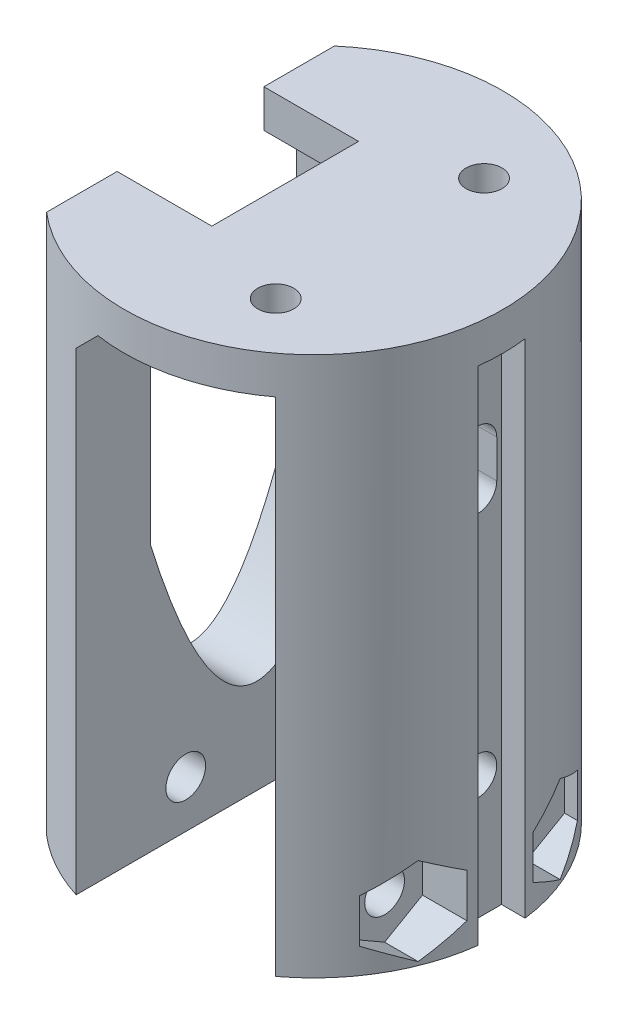
SolidWorks part; units mm, degrees
ref_plane "Front Plane" through (0, 0, 0) normal (0, 0, 1) x (1, 0, 0)
ref_plane "Top Plane" through (0, 0, 0) normal (0, 1, 0) x (1, 0, 0)
ref_plane "Right Plane" through (0, 0, 0) normal (1, 0, 0) x (0, 0, -1)
sketch "Sketch2" plane through (0, 0, 0) normal (0, 1, 0) x (1, 0, 0)
  line L0 (-3.81, 25.1126) -> (-3.81, -25.1126) construction
  line L1 (-16.51, -19.3023) -> (-16.51, -9.8425)
  line L2 (-20.6326, -9.8425) -> (16.7847, -9.8425) construction
  line L3 (-16.51, -9.8425) -> (-3.81, -9.8425)
  line L4 (-3.81, -9.8425) -> (-3.81, 9.8425)
  line L5 (16.7847, 9.8425) -> (-20.6326, 9.8425) construction
  line L6 (-3.81, 9.8425) -> (-16.51, 9.8425)
  line L7 (-16.51, 9.8425) -> (-16.51, 19.3023)
  line L8 (-16.51, -19.3023) -> (-16.51, 19.3023) construction
  circle A2 centre (0, 0) radius 25.4 construction
  arc A3 (-16.51, -19.3023) -> (-16.51, 19.3023) centre (0, 0) ccw
  dimension "D1" = 3.81
  dimension "D2" = 16.51
  dimension "D3" = 25.4
extrude "plate" add sketch "Sketch2" along normal blind 5.08
sketch "Sketch15" plane through (0, 0, 0) normal (0, -1, 0) x (1, 0, 0)
  circle A1 centre (8.89, 13.97) radius 2.413
  circle A2 centre (8.89, 13.97) radius 2.413 construction
  circle A3 centre (8.89, -13.97) radius 2.413
  circle A4 centre (8.89, -13.97) radius 2.413 construction
extrude "boltholes" cut sketch "Sketch15" against normal up to next
sketch "Sketch16" plane through (0, 0, 0) normal (0, -1, 0) x (1, 0, 0)
  line L5 (25.2008, 3.175) -> (25.2008, -3.175) construction
  line L6 (15.24, 20.32) -> (15.24, -20.32)
  line L12 (0, 0) -> (25.2008, 0) construction
  line L13 (25.2008, 3.175) -> (22.0258, 3.175)
  line L14 (22.0258, 3.175) -> (22.0258, -3.175)
  line L15 (22.0258, -3.175) -> (25.2008, -3.175)
  arc A0 (-16.51, -19.3023) -> (-16.51, 19.3023) centre (0, 0) ccw construction
  arc A2 (15.24, 20.32) -> (25.2008, 3.175) centre (0, 0) cw
  arc A3 (15.24, -20.32) -> (25.2008, -3.175) centre (0, 0) ccw
  dimension "D1" = 6.35
  dimension "D4" = 15.24
  dimension "D2" = 3.175
extrude "upright" add sketch "Sketch16" along normal blind 67.31
sketch "Sketch19" plane through (0, 0, 0) normal (0, -1, 0) x (1, 0, 0)
  line L0 (-16.51, 14.2223) -> (-7.62, 14.2223)
  line L1 (-16.51, 9.8425) -> (-16.51, 19.3023) construction
  line L2 (-7.62, 14.2223) -> (-7.62, 24.2301)
  line L3 (-16.51, 19.3023) -> (-16.51, 14.2223)
  line L4 (-3.81, 0) -> (15.24, 0) construction
  line L5 (-3.81, -9.8425) -> (-3.81, 9.8425) construction
  line L6 (15.24, 20.32) -> (15.24, -20.32) construction
  line L7 (-7.62, -14.2223) -> (-7.62, -24.2301)
  line L8 (-16.51, -14.2223) -> (-7.62, -14.2223)
  line L9 (-16.51, -19.3023) -> (-16.51, -14.2223)
  line L10 (15.24, 20.32) -> (15.24, -20.32) construction
  arc A0 (15.24, 20.32) -> (-16.51, 19.3023) centre (0, 0) ccw construction
  arc A1 (-16.51, 19.3023) -> (-7.62, 24.2301) centre (0, 0) cw
  arc A2 (-16.51, -19.3023) -> (-7.62, -24.2301) centre (0, 0) ccw
  dimension "D1" = 8.89
  dimension "D2" = 5.08
  dimension "D3" = 22.86
  dimension "D4" = 7.62
extrude "second_side_legs" add sketch "Sketch19" along normal blind 31.75
sketch "Sketch20" plane through (0, -31.75, 0) normal (0, -1, 0) x (1, 0, 0)
  line L0 (-16.51, 19.3023) -> (-16.51, -19.3023)
  line L1 (-7.62, 24.2301) -> (-7.62, -24.2301)
  arc A0 (-16.51, 19.3023) -> (-7.62, 24.2301) centre (0, 0) cw
  arc A1 (-16.51, -19.3023) -> (-7.62, -24.2301) centre (0, 0) ccw
extrude "second_side_face" add sketch "Sketch20" along normal up to surface (35.56 mm away) up to face at (21.4029, -67.31, 0)
sketch "Sketch21" plane through (-16.51, 0, 0) normal (-1, 0, 0) x (0, 0, 1)
  line L0 (14.2223, -31.75) -> (-14.2223, -31.75) construction
  line L1 (-14.2223, -31.75) -> (-14.2223, 0) construction
  line L2 (0, -31.75) -> (0, -52.3979) construction
  line L3 (-14.2223, -31.75) -> (14.2223, -31.75)
  parabola Q0 (-14.2223, -31.75) -> (14.2223, -31.75) focus (0, -52.3979) apex (0, -54.61)
  dimension "D1" = 22.86
extrude "archway" cut sketch "Sketch21" against normal up to next
sketch "Sketch17" plane through (15.24, 0, 0) normal (-1, 0, 0) x (0, 0, 1)
  line L0 (0, 0) -> (0, -67.31) construction
  line L1 (-9.8425, 0) -> (9.8425, 0) construction
  line L2 (-3.175, -67.31) -> (3.175, -67.31) construction
  line L3 (0, -12.7) -> (0, -17.78) construction
  line L4 (2.54, -12.7) -> (2.54, -17.78)
  line L5 (-2.54, -12.7) -> (-2.54, -17.78)
  line L6 (-9.525, -60.96) -> (9.525, -60.96) construction
  arc A1 (2.54, -12.7) -> (-2.54, -12.7) centre (0, -12.7) ccw
  arc A2 (-2.54, -17.78) -> (2.54, -17.78) centre (0, -17.78) ccw
  circle A3 centre (0, -50.8) radius 2.54
  circle A6 centre (-9.525, -60.96) radius 2.667
  circle A7 centre (9.525, -60.96) radius 2.667
  point P8 (0, -15.24)
  point P17 (0, -60.96)
  dimension "D1" = 5.08
  dimension "D3" = 12.7
  dimension "D4" = 5.08
  dimension "D6" = 10.16
  dimension "D7" = 19.05
  dimension "D8" = 5.334
  dimension "D9" = 5.334
  dimension "D2" = 5.08
  dimension "D5" = 38.1
extrude "upright_holes" cut sketch "Sketch17" along normal through all both and the other way through all
sketch "Sketch22" plane through (15.24, 0, 0) normal (-1, 0, 0) x (0, 0, 1)
  line L1 (-9.525, -55.0941) -> (-14.605, -58.0271)
  line L2 (-14.605, -58.0271) -> (-14.605, -63.8929)
  line L3 (-14.605, -63.8929) -> (-9.525, -66.8259)
  line L4 (-9.525, -66.8259) -> (-4.445, -63.8929)
  line L5 (-4.445, -63.8929) -> (-4.445, -58.0271)
  line L6 (-4.445, -58.0271) -> (-9.525, -55.0941)
  line L7 (9.525, -55.0941) -> (4.445, -58.0271)
  line L8 (4.445, -58.0271) -> (4.445, -63.8929)
  line L9 (4.445, -63.8929) -> (9.525, -66.8259)
  line L10 (9.525, -66.8259) -> (14.605, -63.8929)
  line L11 (14.605, -63.8929) -> (14.605, -58.0271)
  line L12 (14.605, -58.0271) -> (9.525, -55.0941)
  circle A0 centre (-9.525, -60.96) radius 5.08 construction
  circle A1 centre (9.525, -60.96) radius 5.08 construction
  dimension "D1" = 10.16
  dimension "D2" = 10.16
extrude "lower_connecting_boltholes" cut sketch "Sketch22" against normal blind 6.35 from offset 3.81 offset against normal yes
chamfer "Chamfer1" distance 3.81 angle 45 2 edges at (-7.62, 0, -19.2262) (-7.62, 0, 19.2262)
